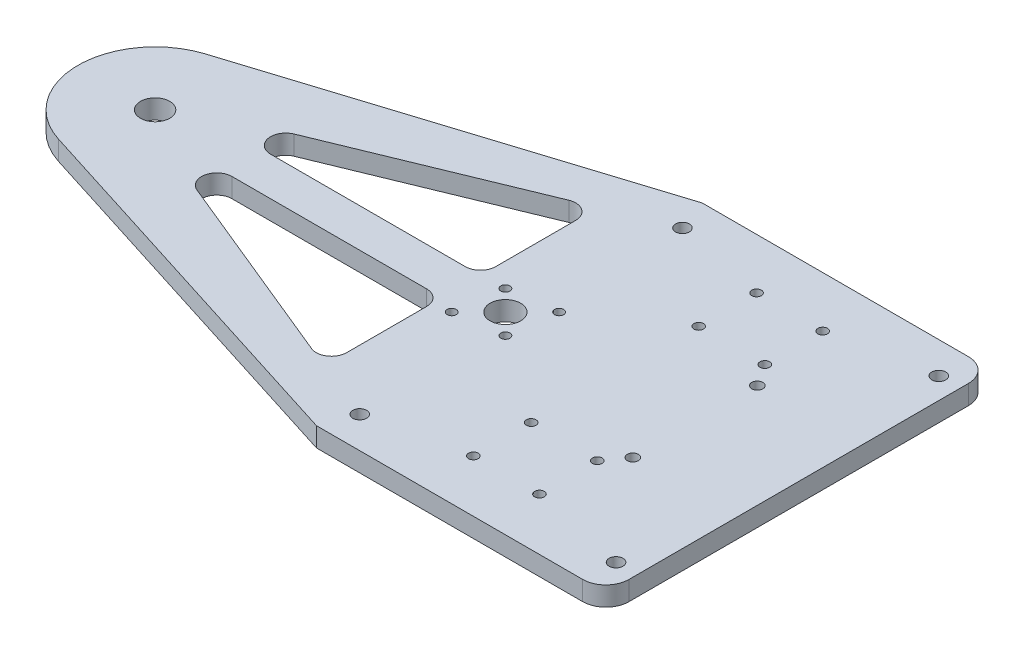
SolidWorks part; units mm, degrees
ref_plane "Front Plane" through (0, 0, 0) normal (0, 0, 1) x (1, 0, 0)
ref_plane "Top Plane" through (0, 0, 0) normal (0, 1, 0) x (1, 0, 0)
ref_plane "Right Plane" through (0, 0, 0) normal (1, 0, 0) x (0, 0, -1)
sketch "Sketch1" plane through (0, 0, 0) normal (0, 1, 0) x (1, 0, 0)
  line L0 (-47.625, 0) -> (47.625, 0) construction
  line L1 (-47.625, -63.5) -> (47.625, -63.5)
  line L2 (-47.625, -63.5) -> (-47.625, 63.5)
  line L3 (-47.625, 63.5) -> (47.625, 63.5)
  line L4 (47.625, -63.5) -> (47.625, 63.5)
  line L5 (-47.625, -63.5) -> (47.625, 63.5) construction
  line L6 (-47.625, 63.5) -> (47.625, -63.5) construction
  point P0 (0, 0)
  dimension "D1" = 95.25
  dimension "D2" = 127
  dimension "D3" = 63.5
extrude "Boss-Extrude1" add sketch "Sketch1" along normal blind 6.35
sketch "Sketch4" plane through (0, 6.35, 0) normal (0, 1, 0) x (1, 0, 0)
  line L1 (-47.625, 63.5) -> (-171.916, 24.2193)
  line L5 (-47.625, 63.5) -> (-47.625, -63.5) construction
  line L9 (-47.625, -63.5) -> (-171.916, -24.2193)
  line L10 (-47.625, 63.5) -> (-47.625, -63.5)
  arc A0 (-171.916, 24.2193) -> (-171.916, -24.2193) centre (-164.2618, 0) ccw
  circle A1 centre (-48.9458, 0) radius 2.5 construction
  dimension "D1" = 50.8
  dimension "D2" = 115.316
extrude "Boss-Extrude3" add sketch "Sketch4" against normal blind 6.35
sketch "Sketch5" plane through (0, 6.35, 0) normal (0, 1, 0) x (1, 0, 0)
  line L0 (-48.9458, 0) -> (-31.7264, 0) construction
  line L3 (-48.9458, 0) -> (-91.3931, 0) construction
  circle A0 centre (-164.2618, 0) radius 4.826
  circle A1 centre (-48.9458, 0) radius 5.04
  arc A2 (-171.916, 24.2193) -> (-171.916, -24.2193) centre (-164.2618, 0) ccw construction
  arc A3 (-171.916, 24.2193) -> (-171.916, -24.2193) centre (-164.2618, 0) ccw
  circle A4 centre (-42.2283, -6.7175) radius 1.5
  circle A5 centre (-40.107, 8.8388) radius 1.5
  circle A6 centre (-57.7846, -8.8388) radius 1.5
  circle A7 centre (-55.6633, 6.7175) radius 1.5
  circle A8 centre (-40.107, 8.8388) radius 1.5 construction
  circle A9 centre (-55.6633, 6.7175) radius 1.5 construction
  circle A10 centre (-57.7846, -8.8388) radius 1.5 construction
  circle A11 centre (-42.2283, -6.7175) radius 1.5 construction
  point P20 (-48.9458, 0)
  dimension "D1" = 9.652
  dimension "D2" = 17.2194
  dimension "D4" = 48.9458
  dimension "D3" = 10.08
extrude "Cut-Extrude1" cut sketch "Sketch5" against normal through all contours A0 | A1 | A5 | A6 | A7 | A4 region at (-164.2618, 6.35, 0) region at (-48.9458, 6.35, 0)
sketch "Sketch6" plane through (0, 6.35, 0) normal (0, 1, 0) x (1, 0, 0)
  line L0 (-63.5, 6.35) -> (-63.5, -6.35) construction
  line L1 (-63.5, 45.1637) -> (-157.9118, 6.35)
  line L2 (-157.9118, 6.35) -> (-63.5, 6.35)
  line L3 (-63.5, 6.35) -> (-63.5, 45.1637)
  line L4 (-63.5, -6.35) -> (-63.5, -45.1637)
  line L5 (-63.5, -45.1637) -> (-157.9118, -6.35)
  line L6 (-157.9118, -6.35) -> (-63.5, -6.35)
  line L7 (0, 0) -> (-63.5, 0) construction
  line L8 (-189.6618, 75.5498) -> (-189.6618, -75.5498) construction
  line L9 (-47.625, 63.5) -> (-171.916, 24.2193) construction
  arc A0 (-171.916, 24.2193) -> (-171.916, -24.2193) centre (-164.2618, 0) ccw construction
  point P12 (-189.6618, 0)
  dimension "D1" = 31.75
  dimension "D2" = 12.7
  dimension "D3" = 12.7
  dimension "D4" = 63.5
extrude "Cut-Extrude2" cut sketch "Sketch6" against normal through all
fillet "Fillet9" radius 5 6 edges at (-157.9118, 3.175, 6.35) (-63.5, 3.175, 6.35) (-63.5, 3.175, 45.1637) (-63.5, 3.175, -6.35) (-157.9118, 3.175, -6.35) (-63.5, 3.175, -45.1637)
fillet "Fillet10" radius 7.62 2 edges at (47.625, 3.175, -63.5) (47.625, 3.175, 63.5)
sketch "Sketch7" plane through (0, 6.35, 0) normal (0, 1, 0) x (1, 0, 0)
  circle A0 centre (-43.7773, -53.1254) radius 2.2812
  circle A1 centre (-43.7773, 53.1254) radius 2.2812
  circle A2 centre (40.6023, 53.1254) radius 2.2812
  circle A3 centre (40.6023, -53.1254) radius 2.2812
  circle A4 centre (-43.7773, 53.1254) radius 2.2812 construction
  circle A5 centre (40.6023, 53.1254) radius 2.2812 construction
  circle A6 centre (40.6023, -53.1254) radius 2.2812 construction
  circle A7 centre (-43.7773, -53.1254) radius 2.2812 construction
extrude "Cut-Extrude3" cut sketch "Sketch7" against normal through all
sketch "Sketch8" plane through (0, 6.35, 0) normal (0, 1, 0) x (1, 0, 0)
  circle A0 centre (-13.2098, -27.25) radius 1.5875
  circle A1 centre (8.5646, -27.25) radius 1.5875
  circle A2 centre (8.5646, -46.3) radius 1.5875
  circle A3 centre (-13.2098, -46.3) radius 1.5875
  circle A4 centre (8.7179, 46.8) radius 1.5875
  circle A5 centre (-13.0566, 27.75) radius 1.5875
  circle A6 centre (-13.0566, 46.8) radius 1.5875
  circle A7 centre (8.7179, 27.75) radius 1.5875
  point P16 (-13.0566, 27.75)
  point P17 (8.7179, 27.75)
  point P18 (8.7179, 46.8)
  point P19 (-13.0566, 46.8)
  dimension "D1" = 3.175
extrude "Cut-Extrude4" cut sketch "Sketch8" against normal through all
sketch "Sketch9" plane through (0, 6.35, 0) normal (0, 1, 0) x (1, 0, 0)
  circle A0 centre (13.4994, -20.4978) radius 1.83
  circle A1 centre (13.4995, 20.5026) radius 1.83
extrude "Cut-Extrude5" cut sketch "Sketch9" against normal through all
